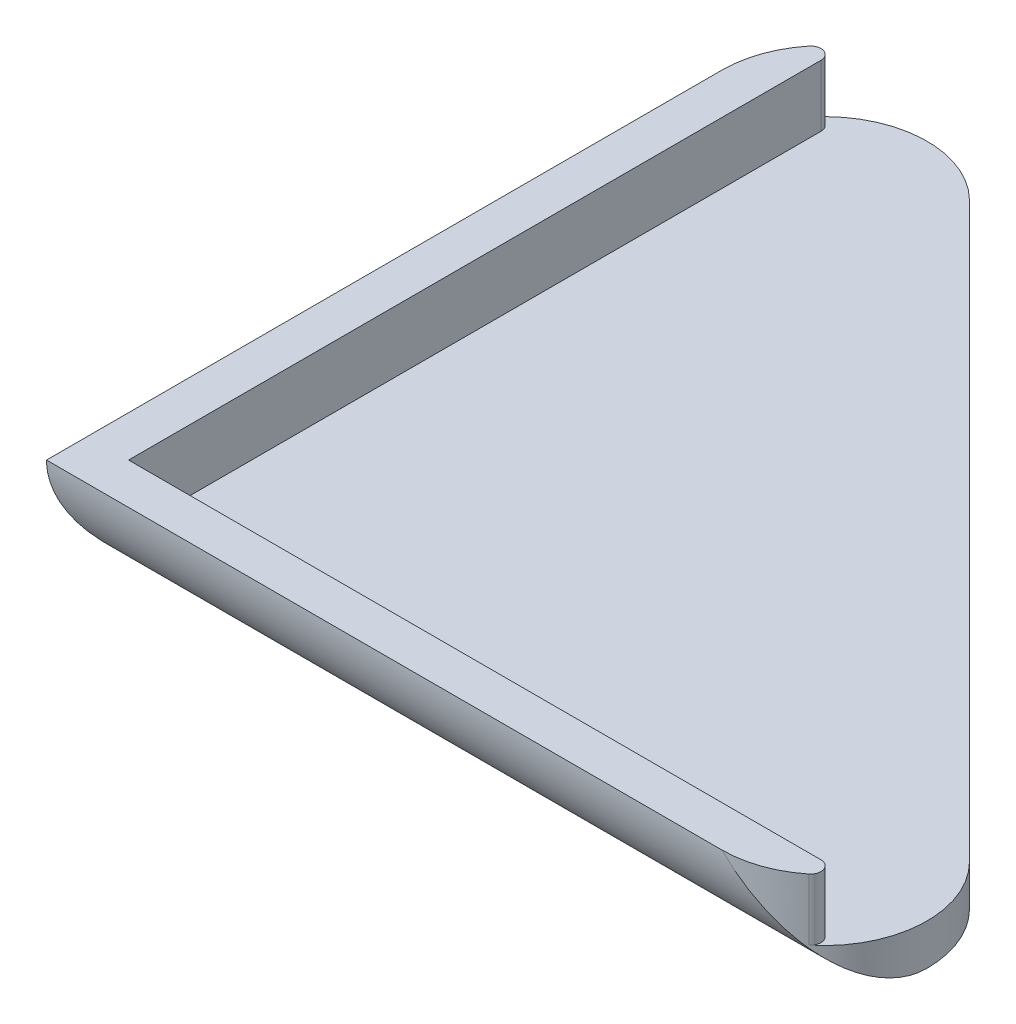
SolidWorks part; units mm, degrees
ref_plane "Front Plane" through (0, 0, 0) normal (0, 0, 1) x (1, 0, 0)
ref_plane "Top Plane" through (0, 0, 0) normal (0, 1, 0) x (1, 0, 0)
ref_plane "Right Plane" through (0, 0, 0) normal (1, 0, 0) x (0, 0, -1)
sketch "Sketch1" plane through (0, 0, 0) normal (0, 1, 0) x (1, 0, 0)
  line L0 (0, 0) -> (0, 45)
  line L1 (0, 45) -> (45, 0)
  line L2 (45, 0) -> (0, 0)
  dimension "D1" = 45
  dimension "D2" = 45
extrude "Boss-Extrude1" add sketch "Sketch1" along normal blind 2
sketch "Sketch2" plane through (0, 2, 0) normal (0, 1, 0) x (1, 0, 0)
  line L0 (2, 43) -> (2, 2)
  line L1 (45, 0) -> (0, 45) construction
  line L2 (2, 2) -> (43, 2)
  line L3 (0, 45) -> (0, 0) construction
  line L4 (0, 0) -> (45, 0) construction
  line L5 (45, 0) -> (43, 2)
  line L8 (0, 0) -> (45, 0)
  line L9 (45, 0) -> (0, 45)
  line L10 (0, 45) -> (0, 0)
  line L11 (0, 0) -> (45, 0)
  line L12 (2, 43) -> (0, 45)
  line L13 (0, 45) -> (0, 0)
  dimension "D1" = 2
  dimension "D2" = 2
  dimension "D3" = 0
extrude "Boss-Extrude2" add sketch "Sketch2" along normal blind 3
sketch "Sketch3" plane through (0, 2, 0) normal (0, 1, 0) x (1, 0, 0)
  line L0 (2, 2) -> (2, 43) construction
  line L1 (43, 2) -> (2, 2) construction
  circle A0 centre (17, 17) radius 5
  dimension "D3" = 10
  dimension "D1" = 15
  dimension "D2" = 15
fillet "Fillet1" radius 5 4 edges at (0, 0, -22.5) (22.5, 0, 0) (45, 2.5, 0) (0, 2.5, -45)
fillet "Fillet2" radius 0.5 2 edges at (2, 3.5, -36.9289) (36.9289, 3.5, -2)
